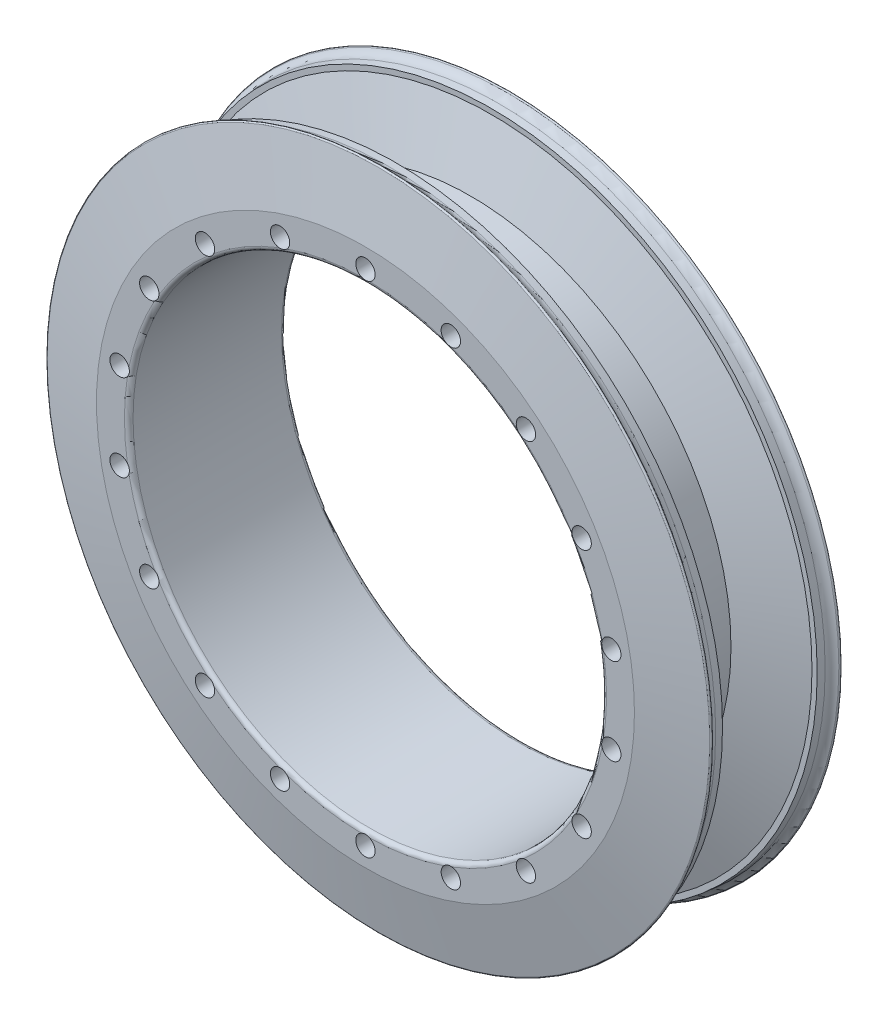
SolidWorks part; units mm, degrees
ref_plane "Alzado" through (0, 0, 0) normal (0, 0, 1) x (1, 0, 0)
ref_plane "Planta" through (0, 0, 0) normal (0, 1, 0) x (1, 0, 0)
ref_plane "Vista lateral" through (0, 0, 0) normal (1, 0, 0) x (0, 0, -1)
sketch "Croquis1" plane through (0, 0, 0) normal (1, 0, 0) x (0, 0, -1)
  line L0 (-496.2723, 0) -> (496.2723, 0) construction
  line L1 (0, 286.5) -> (0, -286.5) construction
  line L2 (-7.6059, 272.5) -> (7.6059, 272.5) construction
  line L3 (-8.0903, 272.876) -> (-8.1612, 273.1529) construction
  line L4 (-8.6072, 273.5275) -> (-12.7183, 273.8437) construction
  line L5 (-15.0067, 276.0215) -> (-16.1941, 285.374)
  line L6 (-16.1941, 285.374) -> (-14.21, 285.626) construction
  line L7 (-15.202, 285.5) -> (-14.4657, 279.7) construction
  line L8 (-14.4657, 279.7) -> (-15.0761, 284.508)
  line L9 (15.202, 285.5) -> (14.4657, 279.7) construction
  line L10 (16.1941, 285.374) -> (14.21, 285.626) construction
  line L11 (14.4657, 279.7) -> (15.0761, 284.508)
  line L12 (15.0067, 276.0215) -> (16.1941, 285.374)
  line L13 (8.6072, 273.5275) -> (12.7183, 273.8437) construction
  line L14 (8.0903, 272.876) -> (8.1612, 273.1529) construction
  line L15 (-11, 272.5) -> (11, 272.5) construction
  line L17 (-11, 272.5) -> (-6.1794, 258.5)
  line L18 (-6.1794, 258.5) -> (6.1794, 258.5)
  line L19 (6.1794, 258.5) -> (11, 272.5)
  line L20 (-11, 272.5) -> (-11, 273.7115)
  line L21 (11, 272.5) -> (11, 273.7115)
  line L22 (11, 273.7115) -> (12.7183, 273.8437)
  line L23 (-11, 273.7115) -> (-12.7183, 273.8437)
  arc A0 (-15.0761, 284.508) -> (-16.1941, 285.374) centre (-15.202, 285.5) ccw
  arc A1 (-14.4657, 279.7) -> (-9.4941, 275) centre (-14.9385, 274.2204) cw
  arc A2 (-9.4941, 275) -> (0, 274.3) centre (0.5356, 346.298) ccw
  arc A3 (-15.0067, 276.0215) -> (-12.7183, 273.8437) centre (-12.5266, 276.3364) ccw
  arc A4 (-7.6059, 272.5) -> (-8.0903, 272.876) centre (-7.6059, 273) cw construction
  arc A5 (-8.1612, 273.1529) -> (-8.6072, 273.5275) centre (-8.6456, 273.029) ccw construction
  arc A6 (9.4941, 275) -> (0, 274.3) centre (-0.5356, 346.298) cw
  arc A7 (8.1612, 273.1529) -> (8.6072, 273.5275) centre (8.6456, 273.029) cw construction
  arc A8 (7.6059, 272.5) -> (8.0903, 272.876) centre (7.6059, 273) ccw construction
  arc A9 (15.0067, 276.0215) -> (12.7183, 273.8437) centre (12.5266, 276.3364) cw
  arc A10 (14.4657, 279.7) -> (9.4941, 275) centre (14.9385, 274.2204) ccw
  arc A11 (15.0761, 284.508) -> (16.1941, 285.374) centre (15.202, 285.5) cw
  point P0 (-15.202, 286.5)
  point P3 (0, 0)
  point P6 (0, 0)
  point P9 (0, 272.5)
  point P25 (-14.75, 274)
  point P28 (-7.9941, 272.5)
  point P31 (-8.25, 273.5)
  point P49 (8.25, 273.5)
  point P50 (7.9941, 272.5)
  point P51 (14.75, 274)
  point P52 (15.202, 286.5)
  point P55 (0, 272.5)
  dimension "D2" = 15.6
  dimension "D7" = 14
  dimension "D8" = 29.5
  dimension "D9" = 6.8
  dimension "D10" = 11.5
  dimension "D11" = 5.5
  dimension "D6" = 2
  dimension "D14" = 72
  dimension "D16" = 2.5
  dimension "D17" = 0.5
  dimension "D1" = 272.5
  dimension "D3" = 1
  dimension "D4" = 548
  dimension "D5" = 8.2
  dimension "D12" = 6.7
  dimension "D13" = 0.7
  dimension "D15" = 6.5
  dimension "D18" = 22
  dimension "D19" = 38
  dimension "D20" = 14
sketch "Croquis2" plane through (0, 0, 0) normal (1, 0, 0) x (0, 0, -1)
  line L0 (-17.25, 253) -> (17.25, 253)
  line L1 (0, 286.5) -> (0, -286.5) construction
  line L2 (-18.25, 254) -> (-18.25, 260.5)
  line L3 (-20.25, 262.5) -> (-23.25, 262.5) construction
  line L4 (-23.25, 262.5) -> (-23.25, 253) construction
  line L5 (-23.25, 198) -> (23.25, 198) construction
  line L6 (23.25, 262.5) -> (23.25, 253) construction
  line L7 (-496.2723, 0) -> (496.2723, 0) construction
  line L8 (0, 286.5) -> (0, -286.5) construction
  line L9 (-18.25, 260.5) -> (-15.227, 274.9669)
  line L10 (11, 273.7115) -> (12.7183, 273.8437) construction
  line L11 (11, 272.5) -> (11, 273.7115) construction
  line L12 (6.1794, 258.5) -> (11, 272.5) construction
  line L13 (-6.1794, 258.5) -> (6.1794, 258.5) construction
  line L14 (-11, 272.5) -> (-6.1794, 258.5) construction
  line L15 (-11, 272.5) -> (-11, 273.7115) construction
  line L16 (-11, 273.7115) -> (-12.7183, 273.8437) construction
  line L17 (11, 273.7115) -> (12.7183, 273.8437)
  line L18 (11, 272.5) -> (11, 273.7115)
  line L19 (6.1794, 258.5) -> (11, 272.5)
  line L20 (-6.1794, 258.5) -> (6.1794, 258.5)
  line L21 (-11, 272.5) -> (-6.1794, 258.5)
  line L22 (-11, 272.5) -> (-11, 273.7115)
  line L23 (-11, 273.7115) -> (-12.7183, 273.8437)
  line L24 (20.25, 262.5) -> (23.25, 262.5) construction
  line L25 (18.25, 254) -> (18.25, 260.5)
  line L26 (18.25, 260.5) -> (15.227, 274.9669)
  arc A0 (-17.25, 253) -> (-18.25, 254) centre (-17.25, 254) cw
  arc A1 (-18.25, 260.5) -> (-20.25, 262.5) centre (-20.25, 260.5) ccw construction
  arc A2 (12.7183, 273.8437) -> (15.0067, 276.0215) centre (12.5266, 276.3364) ccw construction
  arc A3 (-15.0067, 276.0215) -> (-12.7183, 273.8437) centre (-12.5266, 276.3364) ccw construction
  arc A4 (12.7183, 273.8437) -> (14.6755, 275.0588) centre (12.5266, 276.3364) ccw
  arc A5 (-14.6755, 275.0588) -> (-12.7183, 273.8437) centre (-12.5266, 276.3364) ccw
  arc A6 (-14.6755, 275.0588) -> (-15.227, 274.9669) centre (-14.9334, 274.9055) ccw
  arc A7 (14.6755, 275.0588) -> (15.227, 274.9669) centre (14.9334, 274.9055) cw
  arc A8 (18.25, 260.5) -> (20.25, 262.5) centre (20.25, 260.5) cw construction
  arc A9 (17.25, 253) -> (18.25, 254) centre (17.25, 254) ccw
  point P3 (0, 253)
  point P9 (0, 198)
  point P18 (-18.25, 253)
  point P21 (-18.25, 262.5)
  dimension "D6" = 1
  dimension "D7" = 2
  dimension "D8" = 0.3
  dimension "D1" = 35.5
  dimension "D2" = 9.5
  dimension "D3" = 5
  dimension "D4" = 110
  dimension "D5" = 198
revolve "Revolución2" add sketch "Croquis2" angle 360 about L5
sketch "Croquis3" plane through (0, 0, 0) normal (0, 0, 1) x (1, 0, 0)
  circle A0 centre (0, 256) radius 2.25
  circle A1 centre (0, 198) radius 58 construction
  circle A2 centre (19.8372, 252.5022) radius 2.25
  circle A3 centre (37.2817, 242.4306) radius 2.25
  circle A4 centre (50.2295, 227) radius 2.25
  circle A5 centre (57.1188, 208.0716) radius 2.25
  circle A6 centre (57.1188, 187.9284) radius 2.25
  circle A7 centre (50.2295, 169) radius 2.25
  circle A8 centre (37.2817, 153.5694) radius 2.25
  circle A9 centre (19.8372, 143.4978) radius 2.25
  circle A10 centre (0, 140) radius 2.25
  circle A11 centre (-19.8372, 143.4978) radius 2.25
  circle A12 centre (-37.2817, 153.5694) radius 2.25
  circle A13 centre (-50.2295, 169) radius 2.25
  circle A14 centre (-57.1188, 187.9284) radius 2.25
  circle A15 centre (-57.1188, 208.0716) radius 2.25
  circle A16 centre (-50.2295, 227) radius 2.25
  circle A17 centre (-37.2817, 242.4306) radius 2.25
  circle A18 centre (-19.8372, 252.5022) radius 2.25
  arc A19 (0, 256) -> (19.8372, 252.5022) centre (0, 198) cw
  point P6 (10.0716, 255.1188)
  point P41 (0, 198)
  dimension "D1" = 4.5
  dimension "D2" = 58
  dimension "D3" = 18
extrude "Cortar-Extruir1" cut sketch "Croquis3" along normal through all from offset 6.18 contours A12 | A11 | A13 | A10 | A9 | A8 | A7 | A6 | A5 | A4 | A3 | A2 | A0 | A14 | A15 | A16 | A17 | A18 offset against normal yes
sketch "Croquis4" plane through (0, 0, 0) normal (0, 0, 1) x (1, 0, 0)
  circle A0 centre (10.0716, 255.1188) radius 2.25
  circle A1 centre (0, 198) radius 58 construction
  circle A2 centre (0, 198) radius 58 construction
  circle A3 centre (29, 248.2295) radius 2.25
  circle A4 centre (44.4306, 235.2817) radius 2.25
  circle A5 centre (54.5022, 217.8372) radius 2.25
  circle A6 centre (58, 198) radius 2.25
  circle A7 centre (54.5022, 178.1628) radius 2.25
  circle A8 centre (44.4306, 160.7183) radius 2.25
  circle A9 centre (29, 147.7705) radius 2.25
  circle A10 centre (10.0716, 140.8812) radius 2.25
  circle A11 centre (-10.0716, 140.8812) radius 2.25
  circle A12 centre (-29, 147.7705) radius 2.25
  circle A13 centre (-44.4306, 160.7183) radius 2.25
  circle A14 centre (-54.5022, 178.1628) radius 2.25
  circle A15 centre (-58, 198) radius 2.25
  circle A16 centre (-54.5022, 217.8372) radius 2.25
  circle A17 centre (-44.4306, 235.2817) radius 2.25
  circle A18 centre (-29, 248.2295) radius 2.25
  circle A19 centre (-10.0716, 255.1188) radius 2.25
  point P42 (0, 198)
  dimension "D1" = 4.5
  dimension "D2" = 18
extrude "Cortar-Extruir2" cut sketch "Croquis4" against normal through all from offset 6.18
